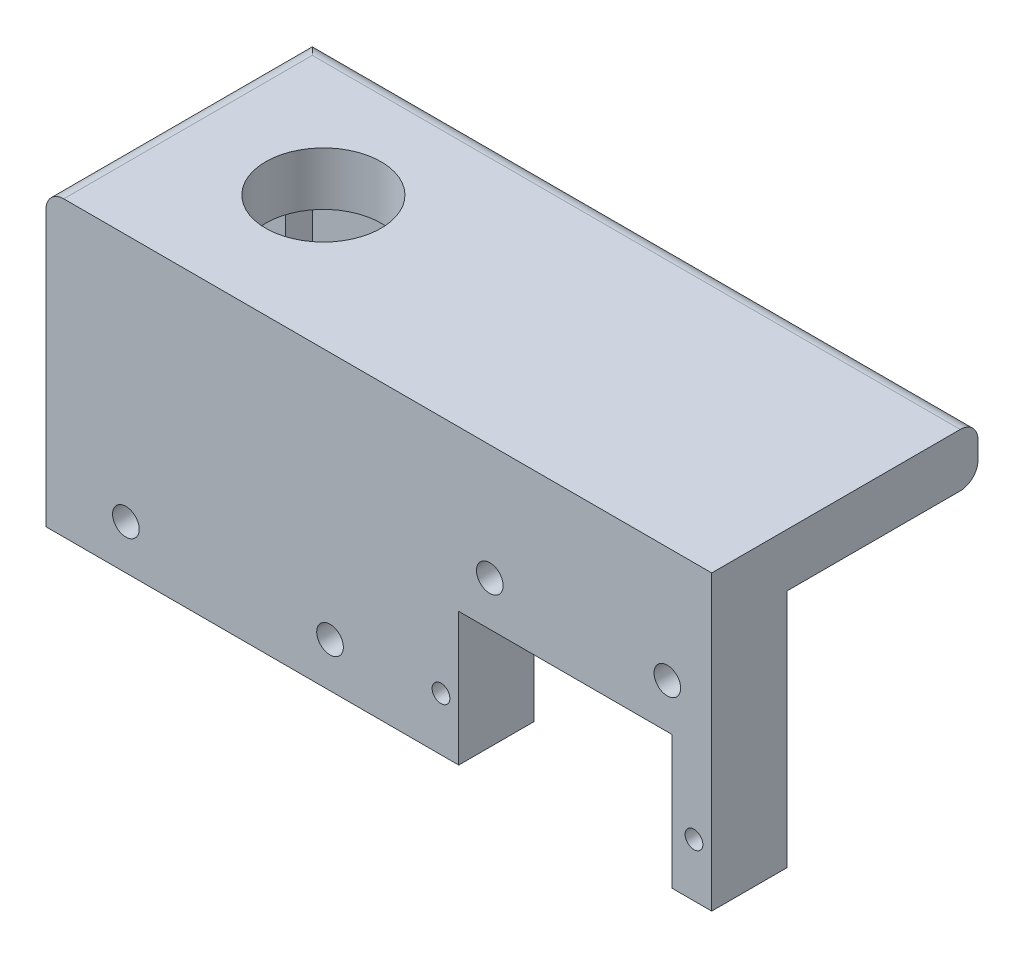
SolidWorks part; units mm, degrees
ref_plane "Front Plane" through (0, 0, 0) normal (0, 0, 1) x (1, 0, 0)
ref_plane "Top Plane" through (0, 0, 0) normal (0, 1, 0) x (1, 0, 0)
ref_plane "Right Plane" through (0, 0, 0) normal (1, 0, 0) x (0, 0, -1)
sketch "Sketch1" plane through (0, -4.342, 0) normal (0, -1, 0) x (1, 0, 0)
  line L0 (-40.9843, 28.2004) -> (-18.4843, 28.2004) construction
  line L1 (-11.5696, 28.2004) -> (-86.5696, 28.2004)
  line L2 (-11.5696, 28.2004) -> (-11.5696, -1.7996)
  line L3 (-11.5696, -1.7996) -> (-86.5696, -1.7996)
  line L4 (-86.5696, 28.2004) -> (-86.5696, -1.7996)
  dimension "D1" = 75
  dimension "D2" = 30
extrude "Boss-Extrude1" add sketch "Sketch1" along normal blind 6 contours L1 L4 L3 L2
sketch "Sketch2" plane through (0, -10.342, 0) normal (0, -1, 0) x (-1, 0, 0)
  line L1 (86.5696, 1.7996) -> (38.5696, 1.7996)
  line L2 (86.5696, 1.7996) -> (86.5696, -2.7004)
  line L3 (86.5696, -2.7004) -> (38.5696, -2.7004)
  line L4 (38.5696, 1.7996) -> (38.5696, -2.7004)
  line L5 (38.5696, 1.7996) -> (43.5696, 1.7996)
  line L6 (38.5696, 1.7996) -> (38.5696, -7.2004)
  line L7 (38.5696, -7.2004) -> (43.5696, -7.2004)
  line L8 (43.5696, 1.7996) -> (43.5696, -7.2004)
  line L9 (11.5696, -28.2004) -> (86.5696, -28.2004) construction
  line L10 (86.5696, 1.7996) -> (82.0696, 1.7996)
  line L11 (86.5696, 1.7996) -> (86.5696, -28.2004)
  line L12 (86.5696, -28.2004) -> (82.0696, -28.2004)
  line L13 (82.0696, 1.7996) -> (82.0696, -28.2004)
  line L14 (11.5696, -28.2004) -> (11.5696, 1.7996) construction
  line L15 (86.5696, -28.2004) -> (40.0696, -28.2004)
  line L16 (86.5696, -28.2004) -> (86.5696, -23.7004)
  line L17 (86.5696, -23.7004) -> (40.0696, -23.7004)
  line L18 (40.0696, -28.2004) -> (40.0696, -23.7004)
  line L19 (46.0696, -28.2004) -> (40.0696, -28.2004)
  line L20 (46.0696, -28.2004) -> (46.0696, -19.7004)
  line L21 (46.0696, -19.7004) -> (40.0696, -19.7004)
  line L22 (40.0696, -28.2004) -> (40.0696, -19.7004)
  line L24 (11.5696, -28.2004) -> (16.0696, -28.2004)
  line L25 (11.5696, -28.2004) -> (11.5696, -19.7004)
  line L26 (11.5696, -19.7004) -> (16.0696, -19.7004)
  line L27 (16.0696, -28.2004) -> (16.0696, -19.7004)
  dimension "D1" = 4.5
  dimension "D2" = 48
  dimension "D3" = 5
  dimension "D4" = 9
  dimension "D5" = 4.5
  dimension "D6" = 4.5
  dimension "D7" = 0
  dimension "D8" = 28.5
  dimension "D9" = 40.5
  dimension "D10" = 8.5
  dimension "D11" = 8.5
  dimension "D12" = 4.5
extrude "Boss-Extrude4" add sketch "Sketch2" along normal blind 27 contours L16 L15 L18 L17 | L2 L1 L4 L3 | L11 L10 L13 L12 | L6 L5 L8 L7 | L20 L19 L22 L21 | L25 L24 L27 L26
sketch "Sketch7" plane through (-38.5696, 0, 0) normal (1, 0, 0) x (0, 0, -1)
  line L1 (-7.2004, -37.342) -> (-2.7004, -37.342)
  line L2 (-7.2004, -37.342) -> (-7.2004, -22.342)
  line L3 (-7.2004, -22.342) -> (-2.7004, -22.342)
  line L4 (-2.7004, -37.342) -> (-2.7004, -22.342)
  dimension "D1" = 15
  dimension "D2" = 4.5
extrude "Cut-Extrude1" cut sketch "Sketch7" against normal blind 6
sketch "Sketch9" plane through (0, -4.342, 0) normal (0, 1, 0) x (1, 0, 0)
  line L1 (-86.5696, -28.2004) -> (-86.5696, 1.7996) construction
  line L2 (-11.5696, 1.7996) -> (-86.5696, 1.7996) construction
  circle A0 centre (-70.3196, -13.2004) radius 6.5
  dimension "D1" = 16.25
  dimension "D2" = 15
  dimension "D3" = 13
extrude "Cut-Extrude2" cut sketch "Sketch9" against normal blind 30
sketch "Sketch10" plane through (0, 0, 28.2004) normal (0, 0, 1) x (1, 0, 0)
  line L0 (-86.5696, -37.342) -> (-86.5696, -4.342) construction
  line L2 (-86.5696, -37.342) -> (-40.0696, -37.342) construction
  circle A0 centre (-77.5696, -32.342) radius 1.5
  dimension "D1" = 9
  dimension "D2" = 3
  dimension "D3" = 5
extrude "Cut-Extrude3" cut sketch "Sketch10" against normal blind 50
sketch "Sketch11" plane through (0, 0, 28.2004) normal (0, 0, 1) x (1, 0, 0)
  line L0 (-86.5696, -37.342) -> (-86.5696, -4.342) construction
  circle A0 centre (-54.5696, -32.342) radius 1.5
  circle A1 centre (-77.5696, -32.342) radius 1.5 construction
  dimension "D1" = 32
  dimension "D2" = 3
  dimension "D3" = 0
extrude "Cut-Extrude4" cut sketch "Sketch11" against normal blind 10
sketch "Sketch12" plane through (-86.5696, 0, 0) normal (-1, 0, 0) x (0, 0, 1)
  line L0 (-1.7996, -37.342) -> (28.2004, -37.342) construction
  line L1 (5.7004, -37.342) -> (20.7004, -37.342)
  line L2 (5.7004, -37.342) -> (5.7004, -11.342)
  line L3 (5.7004, -11.342) -> (20.7004, -11.342)
  line L4 (20.7004, -37.342) -> (20.7004, -11.342)
  line L5 (28.2004, -4.342) -> (-1.7996, -4.342) construction
  point P8 (13.2004, -4.342)
  dimension "D1" = 15
  dimension "D2" = 7.5
  dimension "D3" = 26
extrude "Cut-Extrude5" cut sketch "Sketch12" against normal blind 5
sketch "Sketch14" plane through (-40.0696, 0, 0) normal (1, 0, 0) x (0, 0, -1)
  line L1 (-19.7004, -22.342) -> (-28.2004, -22.342)
  line L2 (-19.7004, -22.342) -> (-19.7004, -10.342)
  line L3 (-19.7004, -10.342) -> (-28.2004, -10.342)
  line L4 (-28.2004, -22.342) -> (-28.2004, -10.342)
  dimension "D1" = 12
extrude "Boss-Extrude6" add sketch "Sketch14" along normal up to vertex (24 mm away) up to point (-16.0696, -10.342, 28.2004)
sketch "Sketch15" plane through (0, 0, 28.2004) normal (0, 0, 1) x (1, 0, 0)
  line L0 (-11.5696, -37.342) -> (-16.0696, -37.342) construction
  line L1 (-11.5696, -37.342) -> (-11.5696, -4.342) construction
  line L2 (-40.0696, -37.342) -> (-40.0696, -22.342) construction
  circle A0 centre (-13.5696, -31.342) radius 1
  circle A1 centre (-42.0696, -31.342) radius 1
  dimension "D1" = 2
  dimension "D2" = 6
  dimension "D3" = 2
  dimension "D4" = 0
  dimension "D5" = 2
  dimension "D6" = 2
extrude "Cut-Extrude6" cut sketch "Sketch15" against normal blind 11
sketch "Sketch16" plane through (0, 0, 19.7004) normal (0, 0, -1) x (-1, 0, 0)
  line L1 (11.5696, -37.342) -> (11.5696, -10.342) construction
  line L2 (16.0696, -22.342) -> (40.0696, -22.342) construction
  circle A0 centre (36.5696, -17.342) radius 1.5
  circle A1 centre (16.5696, -17.342) radius 1.5
  dimension "D1" = 3
  dimension "D2" = 3
  dimension "D3" = 5
  dimension "D4" = 5
  dimension "D5" = 5
  dimension "D6" = 20
extrude "Cut-Extrude7" cut sketch "Sketch16" against normal blind 11
fillet "Fillet1" radius 2 4 edges at (-86.5696, -4.342, 13.2004) (-25.0696, -10.342, -1.7996) (-49.0696, -4.342, -1.7996) (-38.5696, -23.842, -1.7996)
